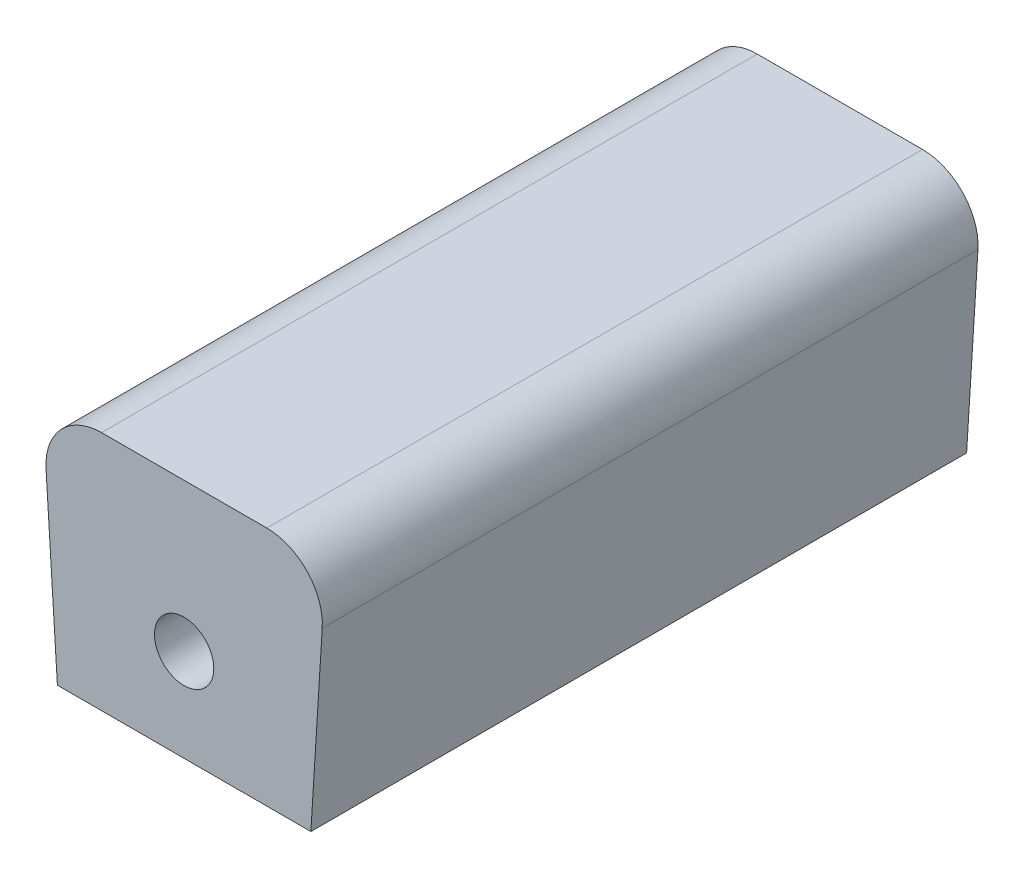
SolidWorks part; units mm, degrees
ref_plane "Front Plane" through (0, 0, 0) normal (0, 0, 1) x (1, 0, 0)
ref_plane "Top Plane" through (0, 0, 0) normal (0, 1, 0) x (1, 0, 0)
ref_plane "Right Plane" through (0, 0, 0) normal (1, 0, 0) x (0, 0, -1)
sketch "Sketch1" plane through (0, 0, 0) normal (0, 0, 1) x (1, 0, 0)
  line L0 (6.6626, -21.6753) -> (9.7812, 28.2232)
  line L1 (5.9786, 32.2709) -> (-5.3535, 32.2709)
  line L2 (-9.1561, 28.2232) -> (-6.0374, -21.6753)
  circle A0 centre (0.3126, -22.8151) radius 2.127
  circle A1 centre (0.3126, 0.0449) radius 2.127
  circle A2 centre (0.3126, 22.1109) radius 2.032
  arc A3 (-6.0374, -21.6753) -> (6.6626, -21.6753) centre (0.3126, -21.5438) ccw
  arc A4 (9.7812, 28.2232) -> (5.9786, 32.2709) centre (5.9786, 28.4609) ccw
  arc A5 (-5.3535, 32.2709) -> (-9.1561, 28.2232) centre (-5.3535, 28.4609) ccw
extrude "Boss-Extrude1" add sketch "Sketch1" along normal blind 44.958
sketch "Sketch2" plane through (0, 0, 44.958) normal (0, 0, 1) x (1, 0, 0)
  line L0 (5.9786, 32.2709) -> (-5.3535, 32.2709) construction
  line L1 (-27.7506, -32.159) -> (33.4121, -32.159)
  line L2 (-27.7506, -32.159) -> (-27.7506, 15.7609)
  line L3 (-27.7506, 15.7609) -> (33.4121, 15.7609)
  line L4 (33.4121, -32.159) -> (33.4121, 15.7609)
  dimension "D1" = 16.51
extrude "Cut-Extrude1" cut sketch "Sketch2" against normal through all
